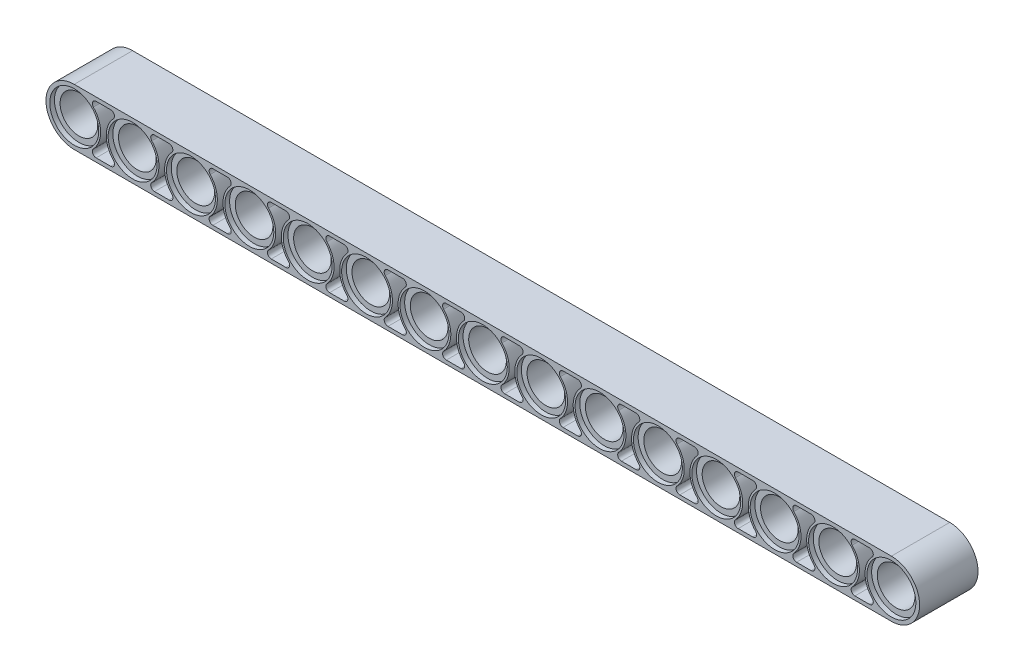
SolidWorks part; units mm, degrees
material "PVC Rigid"
ref_plane "Front Plane" through (0, 0, 0) normal (0, 0, 1) x (1, 0, 0)
ref_plane "Top Plane" through (0, 0, 0) normal (0, 1, 0) x (1, 0, 0)
ref_plane "Right Plane" through (0, 0, 0) normal (1, 0, 0) x (0, 0, -1)
sketch "Sketch1" plane through (0, 0, 0) normal (0, 0, 1) x (1, 0, 0)
  line L0 (-7.874, 0) -> (7.874, 0) construction
  line L1 (7.874, -3.81) -> (-7.874, -3.81)
  line L2 (7.874, 3.81) -> (-7.874, 3.81)
  line L8 (0, 15.1379) -> (0, -14.3507)
  line L9 (3.937, 3.302) -> (3.937, -3.302) construction
  line L10 (3.937, 3.302) -> (3.937, 3.81)
  line L11 (2.9512, -3.302) -> (4.9228, -3.302)
  line L12 (2.9512, 3.302) -> (4.9228, 3.302)
  line L13 (3.937, -3.302) -> (3.937, -3.81)
  line L14 (-3.937, 3.302) -> (-3.937, -3.302) construction
  line L15 (-3.937, -3.302) -> (-3.937, -3.81)
  line L16 (-2.9512, 3.302) -> (-4.9228, 3.302)
  line L17 (-2.9512, -3.302) -> (-4.9228, -3.302)
  line L18 (-3.937, 3.302) -> (-3.937, 3.81)
  arc A0 (7.874, -3.81) -> (7.874, 3.81) centre (7.874, 0) ccw
  circle A1 centre (0, 0) radius 3.302
  circle A2 centre (0, 0) radius 2.54
  circle A3 centre (7.874, 0) radius 3.302
  circle A4 centre (7.874, 0) radius 2.54
  arc A5 (-2.9512, 3.302) -> (-2.5823, 2.4447) centre (-2.9512, 2.794) cw
  arc A7 (-4.9228, 3.302) -> (-5.2917, 2.4447) centre (-4.9228, 2.794) ccw
  arc A8 (-5.2917, -2.4447) -> (-4.9228, -3.302) centre (-4.9228, -2.794) ccw
  arc A11 (2.5823, -2.4448) -> (2.5823, 2.4447) centre (0, 0) ccw
  arc A12 (5.2917, 2.4447) -> (5.2917, -2.4447) centre (7.874, 0) ccw
  arc A13 (2.5823, -2.4448) -> (2.9512, -3.302) centre (2.9512, -2.794) ccw
  arc A14 (-2.5823, -2.4448) -> (-2.9512, -3.302) centre (-2.9512, -2.794) cw
  arc A15 (-5.2917, 2.4447) -> (-5.2917, -2.4447) centre (-7.874, 0) cw
  arc A16 (5.2917, -2.4447) -> (4.9228, -3.302) centre (4.9228, -2.794) cw
  arc A17 (4.9228, 3.302) -> (5.2917, 2.4447) centre (4.9228, 2.794) cw
  arc A18 (2.9512, 3.302) -> (2.5823, 2.4447) centre (2.9512, 2.794) ccw
  arc A19 (-2.5823, -2.4448) -> (-2.5823, 2.4447) centre (0, 0) cw
  circle A20 centre (-7.874, 0) radius 2.54
  circle A21 centre (-7.874, 0) radius 3.302
  arc A22 (-7.874, -3.81) -> (-7.874, 3.81) centre (-7.874, 0) cw
  point P13 (9.525, 0)
  point P14 (0, -3.81)
  point P15 (7.62, 0)
  point P17 (0, 3.302)
  point P18 (19.05, 3.302)
  point P19 (0, -3.302)
  point P20 (19.05, -3.302)
  point P23 (13.843, 0)
  point P25 (23.368, 0)
  point P26 (3.429, 0)
  point P27 (-7.874, -3.302)
  point P28 (7.874, -3.302)
  point P29 (-7.874, 3.302)
  point P30 (7.874, 3.302)
  point P35 (11.811, 0)
  point P60 (11.5175, 1.1139)
  point P67 (0, 3.81)
  dimension "D2" = 7.62
  dimension "D3" = 0.508
  dimension "D4" = 5.08
  dimension "D6" = 11.684
  dimension "D1" = 0.254
  dimension "D5" = 0.508
extrude "Boss-Extrude1" add sketch "Sketch1" along normal blind 3.937 contours A3 A4 | L12 A17 A12 A16 L11 A0 A3 region at (5.9055, -3.7013, 0) region at (4.6654, 0, 0)
ref_plane "Plane2" through (11.684, 0, 0) normal (1, 0, 0) x (0, 0, -1)
extrude "Boss-Extrude2" add sketch "Sketch1<7>" along normal blind 3.937 separate body contours L8 A1 | A2 L8 A1 | A18 L12 L8 A1 L11 A13 A11 | A2 L8 A1 region at (1.9685, -3.7242, 0) region at (-1.9685, -3.7242, 0) region at (-3.2282, 0, 0) region at (0.0738, -2.921, 0)
sketch "Sketch1<7>" plane through (0, 0, 0) normal (0, 0, 1) x (1, 0, 0) same geometry as "Sketch1"
sketch "Sketch2" plane through (0, 0, 0) normal (0, 0, 1) x (1, 0, 0)
  circle A0 centre (7.874, 0) radius 3.302 construction
  circle A1 centre (0, 0) radius 3.302 construction
  circle A2 centre (7.874, 0) radius 3.302
  circle A3 centre (0, 0) radius 3.302
extrude "Cut-Extrude1" cut sketch "Sketch2" along normal blind 0.635
pattern_linear "LPattern1" count 13 spacing 7.874 along (-1, 0, 0) of "Boss-Extrude2", "Cut-Extrude1"
ref_plane "Plane1" through (-47.244, 0, 0) normal (1, 0, 0) x (0, 0, -1)
mirror "Mirror2" about plane through (-47.244, 0, 0) normal (1, 0, 0) of bodies 109 101
combine bodies "Combine1" operation type add bodies to combine 109 106 107
ref_plane "Plane3" through (0, 0, 3.937) normal (0, 0, 1) x (1, 0, 0)
mirror "Mirror3" about plane through (0, 0, 3.937) normal (0, 0, 1) of bodies 108
ref_plane "Plane4" through (-106.172, 0, 0) normal (-1, 0, 0) x (0, 0, 1)
